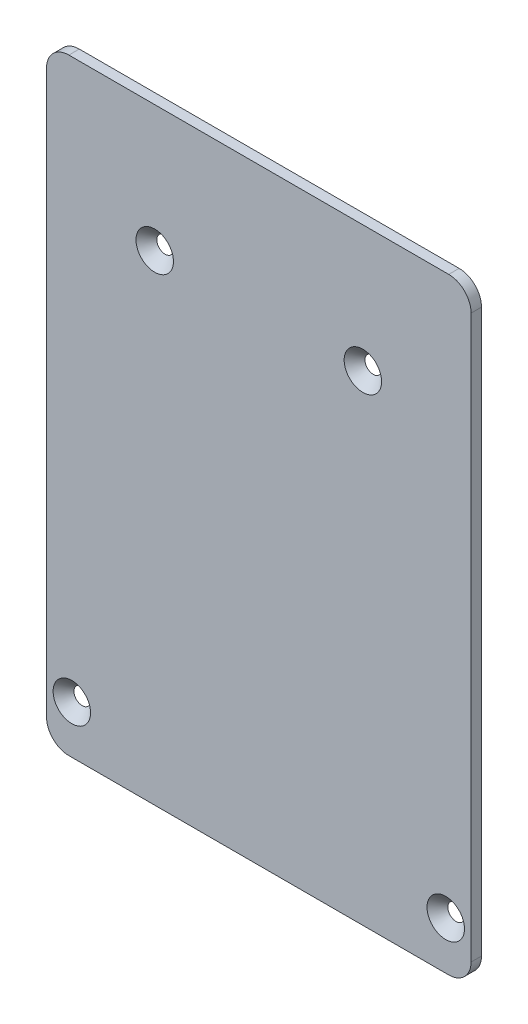
SolidWorks part; units mm, degrees
ref_plane "Plan de face" through (0, 0, 0) normal (0, 0, 1) x (1, 0, 0)
ref_plane "Plan de dessus" through (0, 0, 0) normal (0, 1, 0) x (1, 0, 0)
ref_plane "Plan de droite" through (0, 0, 0) normal (1, 0, 0) x (0, 0, -1)
sketch "Esquisse1" plane through (0, 0, 0) normal (0, 0, 1) x (1, 0, 0)
  line L0 (41, -54) -> (41, 54) construction
  line L1 (36.5, 58.5) -> (-36.5, 58.5) construction
  line L2 (-41, 54) -> (-41, -54) construction
  line L3 (-36.5, -58.5) -> (36.5, -58.5) construction
  line L4 (41, -54) -> (41, 54) construction
  line L5 (36.5, 58.5) -> (-36.5, 58.5) construction
  line L6 (-41, 54) -> (-41, -54) construction
  line L7 (-36.5, -58.5) -> (36.5, -58.5) construction
  line L8 (-36.5, -58.3) -> (36.5, -58.3)
  line L9 (40.8, -54) -> (40.8, 54)
  line L10 (36.5, 58.3) -> (-36.5, 58.3)
  line L11 (-40.8, 54) -> (-40.8, -54)
  arc A0 (36.5, -58.5) -> (41, -54) centre (36.5, -54) ccw construction
  arc A1 (41, 54) -> (36.5, 58.5) centre (36.5, 54) ccw construction
  arc A2 (-36.5, 58.5) -> (-41, 54) centre (-36.5, 54) ccw construction
  arc A3 (-41, -54) -> (-36.5, -58.5) centre (-36.5, -54) ccw construction
  arc A4 (36.5, -58.5) -> (41, -54) centre (36.5, -54) ccw construction
  arc A5 (41, 54) -> (36.5, 58.5) centre (36.5, 54) ccw construction
  arc A6 (-36.5, 58.5) -> (-41, 54) centre (-36.5, 54) ccw construction
  arc A7 (-41, -54) -> (-36.5, -58.5) centre (-36.5, -54) ccw construction
  arc A8 (36.5, -58.3) -> (40.8, -54) centre (36.5, -54) ccw
  arc A9 (40.8, 54) -> (36.5, 58.3) centre (36.5, 54) ccw
  arc A10 (-36.5, 58.3) -> (-40.8, 54) centre (-36.5, 54) ccw
  arc A11 (-40.8, -54) -> (-36.5, -58.3) centre (-36.5, -54) ccw
  circle A12 centre (35.93, -49.1) radius 2.15 construction
  circle A13 centre (35.93, -49.1) radius 2.15 construction
  circle A14 centre (-35.93, -49.1) radius 2.15 construction
  circle A15 centre (-35.93, -49.1) radius 2.15 construction
  circle A16 centre (35.93, -49.1) radius 1.6
  circle A17 centre (-35.93, -49.1) radius 1.6
  circle A18 centre (-20, 34) radius 1.6
  circle A19 centre (20, 34) radius 1.6
  point P36 (0, 0)
  dimension "D2" = 3.2
  dimension "D3" = 20
  dimension "D5" = 3.2
  dimension "D4" = 20
  dimension "D6" = 34
  dimension "D1" = 0.2
extrude "Boss.-Extru.1" add sketch "Esquisse1" against normal blind 2 contours L8 A8 L9 A9 L10 A10 L11 A11 | A16 | A17 | A18 | A19
chamfer "Chanfrein1" distance 2 angle 45 4 edges at (-34.33, -49.1, 0) (37.53, -49.1, 0) (-18.4, 34, 0) (21.6, 34, 0)
